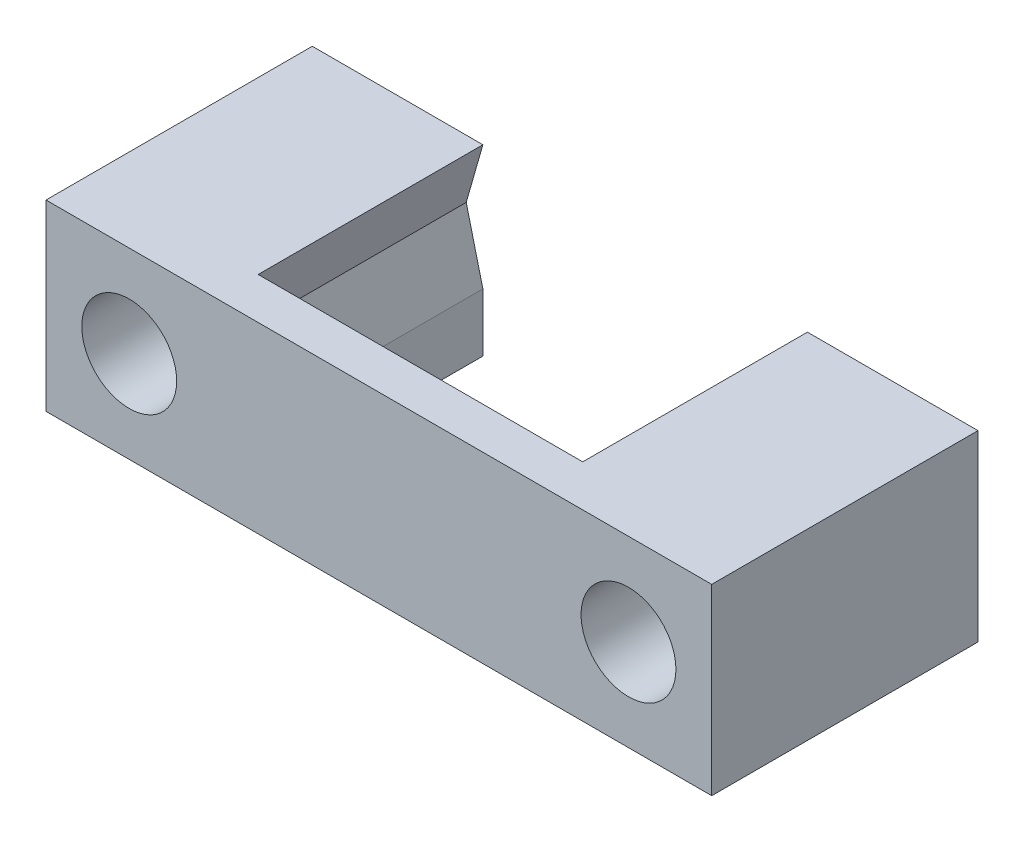
SolidWorks part; units mm, degrees
material "尼龙 101"
ref_plane "前视基准面" through (0, 0, 0) normal (0, 0, 1) x (1, 0, 0)
ref_plane "上视基准面" through (0, 0, 0) normal (0, 1, 0) x (1, 0, 0)
ref_plane "右视基准面" through (0, 0, 0) normal (1, 0, 0) x (0, 0, -1)
other "Configuration Table"
sketch "草图1" plane through (0, 0, 0) normal (0, 0, 1) x (1, 0, 0)
  line L1 (0, 0) -> (40, 0)
  line L2 (0, 0) -> (0, 11)
  line L3 (0, 11) -> (40, 11)
  line L4 (40, 0) -> (40, 11)
  circle A0 centre (5, 5.5) radius 1.6
  circle A1 centre (35, 5.5) radius 1.6
  dimension "D3" = 3.2
  dimension "D4" = 3.2
  dimension "D1" = 40
  dimension "D2" = 11
  dimension "D5" = 5
  dimension "D6" = 5.5
  dimension "D7" = 30
extrude "凸台-拉伸1" add sketch "草图1" along normal blind 14
sketch "草图2" plane through (0, 0, 0) normal (0, 0, -1) x (-1, 0, 0)
  line L0 (-29.75, 11) -> (-30.75, 7.5)
  line L1 (-40, 11) -> (0, 11) construction
  line L2 (-30.75, 7.5) -> (-29.75, 3.5)
  line L3 (-29.75, 3.5) -> (-29.75, 0)
  line L4 (0, 0) -> (-40, 0) construction
  line L5 (-20, 11) -> (-20, 0) construction
  line L6 (-10.25, 3.5) -> (-10.25, 0)
  line L7 (-9.25, 7.5) -> (-10.25, 3.5)
  line L8 (-10.25, 11) -> (-9.25, 7.5)
  line L9 (-10.25, 11) -> (-29.75, 11)
  line L10 (-29.75, 0) -> (-10.25, 0)
  dimension "D1" = 19.5
  dimension "D2" = 21.5
  dimension "D3" = 4
  dimension "D4" = 3.5
extrude "切除-拉伸1" cut sketch "草图2" against normal blind 11.5
sketch "草图3" plane through (0, 0, 14) normal (0, 0, 1) x (1, 0, 0)
  circle A6 centre (5, 5.5) radius 2.85
  circle A7 centre (35, 5.5) radius 2.85
  dimension "D1" = 5.7
extrude "切除-拉伸2" cut sketch "草图3" against normal blind 5
sketch "草图4" plane through (0, 0, 0) normal (0, 0, -1) x (-1, 0, 0)
  line L0 (-10.25, 11) -> (-9.25, 7.5) construction
  line L1 (-9.25, 7.5) -> (-10.25, 3.5) construction
  line L2 (-10.25, 3.5) -> (-10.25, 0) construction
  line L3 (-10.25, 0) -> (0, 0) construction
  line L4 (0, 0) -> (0, 11) construction
  line L5 (0, 11) -> (-10.25, 11) construction
  line L6 (-29.75, 0) -> (-29.75, 3.5) construction
  line L7 (-29.75, 3.5) -> (-30.75, 7.5) construction
  line L8 (-30.75, 7.5) -> (-29.75, 11) construction
  line L9 (-29.75, 11) -> (-40, 11) construction
  line L10 (-40, 11) -> (-40, 0) construction
  line L11 (-40, 0) -> (-29.75, 0) construction
  line L12 (-10.25, 11) -> (-9.25, 7.5)
  line L13 (-9.25, 7.5) -> (-10.25, 3.5)
  line L14 (-10.25, 3.5) -> (-10.25, 0)
  line L15 (-10.25, 0) -> (0, 0)
  line L16 (0, 0) -> (0, 11)
  line L17 (0, 11) -> (-10.25, 11)
  line L18 (-29.75, 0) -> (-29.75, 3.5)
  line L19 (-29.75, 3.5) -> (-30.75, 7.5)
  line L20 (-30.75, 7.5) -> (-29.75, 11)
  line L21 (-29.75, 11) -> (-40, 11)
  line L22 (-40, 11) -> (-40, 0)
  line L23 (-40, 0) -> (-29.75, 0)
  circle A0 centre (-5, 5.5) radius 1.6 construction
  circle A1 centre (-35, 5.5) radius 1.6 construction
  circle A2 centre (-5, 5.5) radius 1.6
  circle A3 centre (-35, 5.5) radius 1.6
extrude "凸台-拉伸2" add sketch "草图4" along normal blind 2
